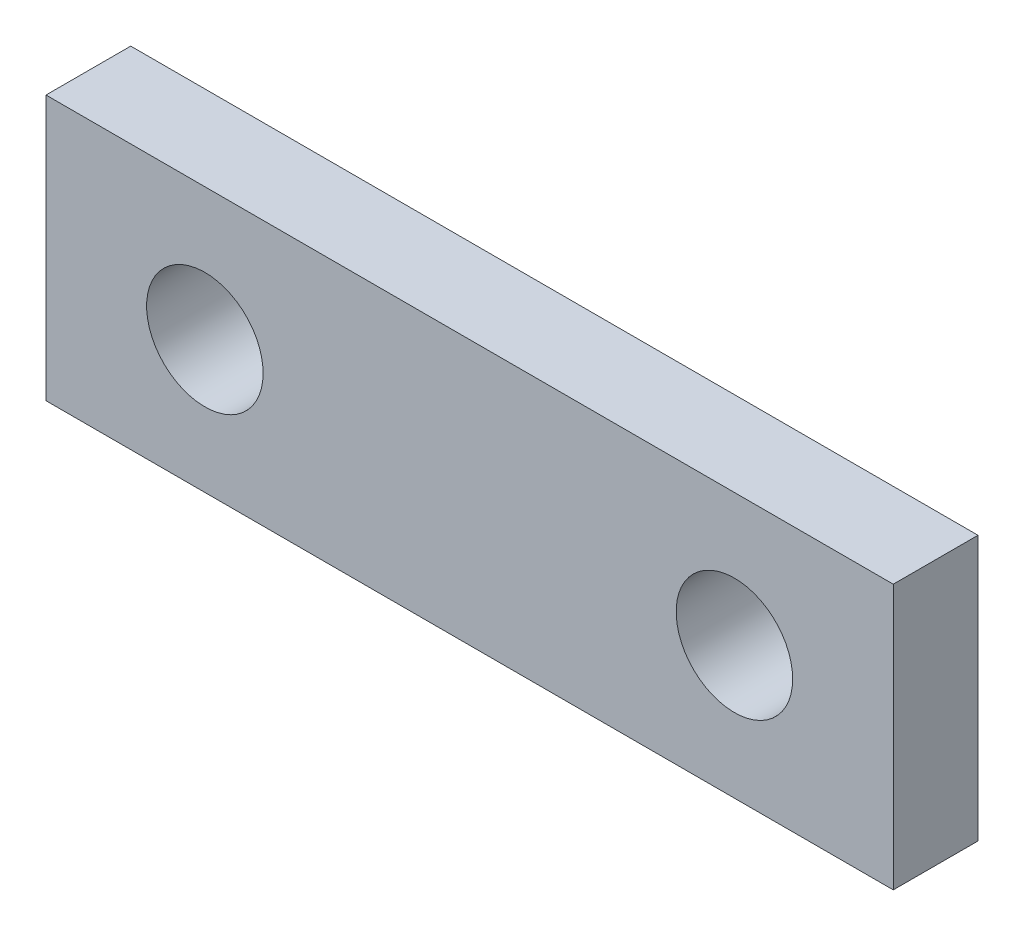
SolidWorks part; units mm, degrees
material "1.0037 (S235JR)"
ref_plane "E_Rechts" through (0, 0, 0) normal (0, 0, 1) x (1, 0, 0)
ref_plane "E_Vorne" through (0, 0, 0) normal (0, 1, 0) x (1, 0, 0)
ref_plane "E_Oben" through (0, 0, 0) normal (1, 0, 0) x (0, 0, -1)
sketch "Skizze1" plane through (0, 0, 0) normal (0, 0, 1) x (1, 0, 0)
  line L0 (55, 0) -> (-55, 0) construction
  line L1 (-40, 12.5) -> (40, 12.5)
  line L2 (-40, 12.5) -> (-40, -12.5)
  line L3 (-40, -12.5) -> (40, -12.5)
  line L4 (40, 12.5) -> (40, -12.5)
  line L5 (0, -55) -> (0, 55) construction
  circle A0 centre (-25, 0) radius 5.5
  circle A1 centre (25, 0) radius 5.5
  dimension "D7" = 11
  dimension "D8" = 11
  dimension "D1" = 80
  dimension "D2" = 25
  dimension "D3" = 12.5
  dimension "D4" = 40
  dimension "D5" = 50
  dimension "D6" = 25
extrude "Aufsatz-Linear austragen1" add sketch "Skizze1" along normal mid plane 8
